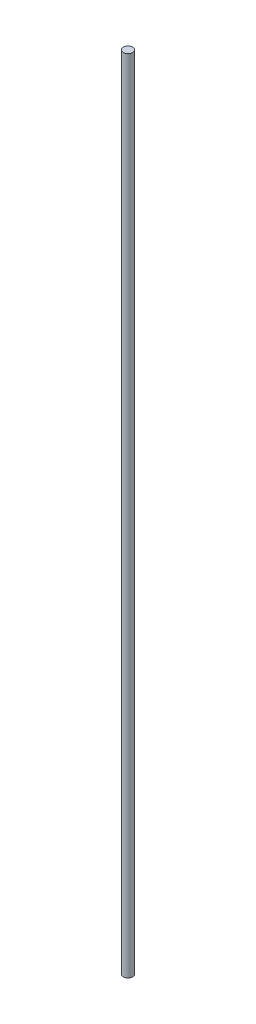
SolidWorks part; units mm, degrees
material "AISI 1020"
ref_plane "Front Plane" through (0, 0, 0) normal (0, 0, 1) x (1, 0, 0)
ref_plane "Top Plane" through (0, 0, 0) normal (0, 1, 0) x (1, 0, 0)
ref_plane "Right Plane" through (0, 0, 0) normal (1, 0, 0) x (0, 0, -1)
sketch "Sketch1" plane through (0, 0, 0) normal (0, 1, 0) x (1, 0, 0)
  circle A0 centre (0, 0) radius 1.5
  dimension "D1" = 3
extrude "Boss-Extrude1" add sketch "Sketch1" along normal blind 128 and the other way blind 128
cosmetic thread "Cosmetic Thread1"
